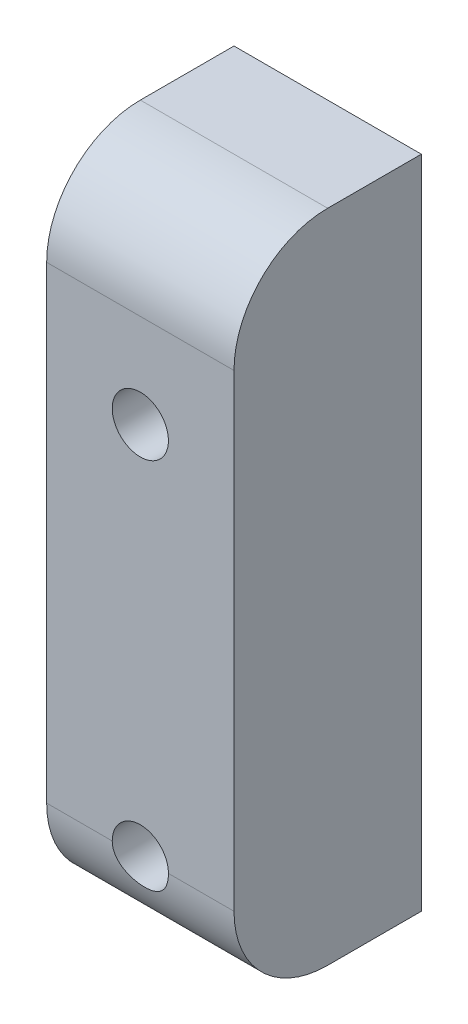
SolidWorks part; units mm, degrees
ref_plane "Front Plane" through (0, 0, 0) normal (0, 0, 1) x (1, 0, 0)
ref_plane "Top Plane" through (0, 0, 0) normal (0, 1, 0) x (1, 0, 0)
ref_plane "Right Plane" through (0, 0, 0) normal (1, 0, 0) x (0, 0, -1)
sketch "Sketch1" plane through (0, 0, 0) normal (0, 0, 1) x (1, 0, 0)
  line L1 (0, 0) -> (10, 0)
  line L2 (0, 0) -> (0, 35)
  line L3 (0, 35) -> (10, 35)
  line L4 (10, 0) -> (10, 35)
  circle A0 centre (5, 25) radius 1.5
  circle A1 centre (5, 5) radius 1.5
  dimension "D3" = 3
  dimension "D4" = 3
  dimension "D1" = 35
  dimension "D2" = 10
  dimension "D5" = 5
  dimension "D6" = 20
extrude "Boss-Extrude1" add sketch "Sketch1" along normal blind 10
fillet "Fillet1" radius 5 1 edges at (5, 0, 10)
fillet "Fillet2" radius 5 1 edges at (5, 35, 10)
